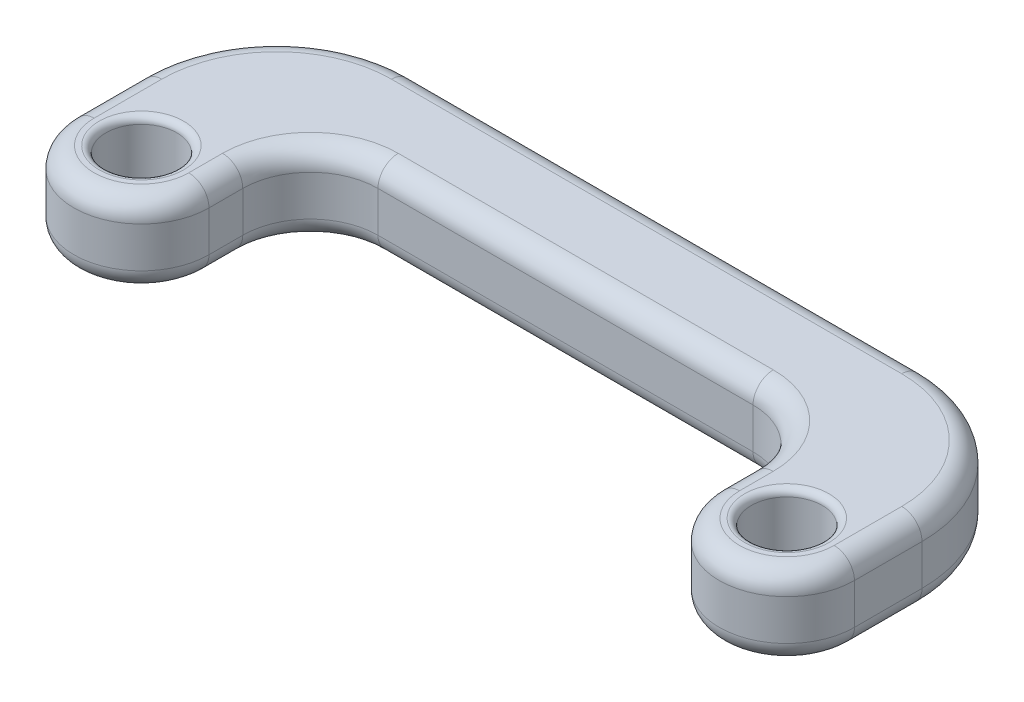
SolidWorks part; units mm, degrees
ref_plane "Front Plane" through (0, 0, 0) normal (0, 0, 1) x (1, 0, 0)
ref_plane "Top Plane" through (0, 0, 0) normal (0, 1, 0) x (1, 0, 0)
ref_plane "Right Plane" through (0, 0, 0) normal (1, 0, 0) x (0, 0, -1)
sketch "Sketch7" plane through (0, 0, 0) normal (0, 1, 0) x (1, 0, 0)
  line L2 (-105.5, 0) -> (-105.5, 30)
  line L3 (-85.5, 0) -> (-85.5, 15)
  line L4 (-105.5, 30) -> (-85.5, 30)
  line L6 (-85.5, 30) -> (10, 30)
  line L7 (-85.5, 15) -> (-10, 15)
  line L10 (10, 0) -> (10, 30.0013)
  line L11 (-10, 0) -> (-10, 15)
  line L12 (10, 30.0013) -> (-10, 30.0013)
  line L13 (-10, 30) -> (-10, 30.0013)
  arc A0 (-10, 0) -> (10, 0) centre (0, 0) ccw
  arc A1 (-105.5, 0) -> (-85.5, 0) centre (-95.5, 0) ccw
  circle A2 centre (-95.5, 0) radius 5
extrude "Boss-Extrude5" add sketch "Sketch7" along normal blind 12 contours L2 A1 L3 L7 L11 A0 L10 L6 L4 A2 region at (-46.2897, 0, -16.412)
sketch "Sketch8" plane through (0, 12, 0) normal (0, 1, 0) x (1, 0, 0)
  circle A0 centre (0, 0) radius 6
fillet "Fillet2" radius 20 2 edges at (10, 6, -30) (-105.5, 6, -30)
fillet "Fillet3" radius 10 2 edges at (-10, 6, -15) (-85.5, 6, -15)
fillet "Fillet5" radius 3 24 edges at (-47.75, 12, -30) (4.1421, 12, -24.1421) (10, 12, -5) (0, 12, 10) (-10, 12, -2.5) (-12.9289, 12, -12.0711) (-47.75, 12, -15) (-82.5711, 12, -12.0711) (-85.5, 12, -2.5) (-95.5, 12, 10) (-105.5, 12, -5) (-105.5, 0, -5) (-95.5, 0, 10) (-85.5, 0, -2.5) (-82.5711, 0, -12.0711) (-47.75, 0, -15) (-12.9289, 0, -12.0711) (-10, 0, -2.5) (0, 0, 10) (10, 0, -5) (4.1421, 0, -24.1421) (-47.75, 0, -30) (-99.6421, 12, -24.1421) (-99.6421, 0, -24.1421)
sketch "Sketch10" plane through (0, 12, 0) normal (0, 1, 0) x (1, 0, 0)
  circle A0 centre (-95.5, 0) radius 5.1
sketch "Sketch11" plane through (0, 0, 0) normal (0, -1, 0) x (1, 0, 0)
  circle A0 centre (-95.5, 0) radius 5.25
  circle A1 centre (0, 0) radius 5.25
extrude "Cut-Extrude1" cut sketch "Sketch11" against normal blind 36
fillet "Fillet6" radius 1 4 edges at (-95.5, 12, 5.25) (0, 12, 5.25) (0, 0, -5.25) (-95.5, 0, -5.25)
